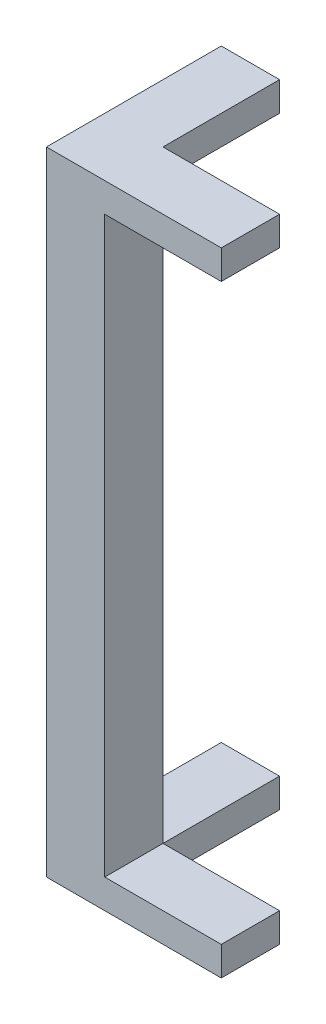
SolidWorks part; units mm, degrees
ref_plane "Front Plane" through (0, 0, 0) normal (0, 0, 1) x (1, 0, 0)
ref_plane "Top Plane" through (0, 0, 0) normal (0, 1, 0) x (1, 0, 0)
ref_plane "Right Plane" through (0, 0, 0) normal (1, 0, 0) x (0, 0, -1)
sketch "Sketch1" plane through (0, 0, 0) normal (0, 1, 0) x (1, 0, 0)
  line L1 (0, 0) -> (30, 0)
  line L2 (0, 0) -> (0, 10)
  line L3 (0, 10) -> (30, 10)
  line L4 (30, 0) -> (30, 10)
  line L5 (0, 0) -> (10, 0)
  line L6 (0, 0) -> (0, 30)
  line L7 (0, 30) -> (10, 30)
  line L8 (10, 0) -> (10, 30)
  dimension "D1" = 10
  dimension "D2" = 10
  dimension "D3" = 30
  dimension "D4" = 30
extrude "Boss-Extrude1" add sketch "Sketch1" along normal blind 10 contours L3 L8 L7 L6 | L1 L8 L3 L2 | L8 L1 L4 L3 region at (5, 0, -5) region at (20, 0, -5) region at (5, 0, -20)
sketch "Sketch2" plane through (0, 10, 0) normal (0, 1, 0) x (1, 0, 0)
  line L1 (0, 0) -> (10, 0)
  line L2 (0, 0) -> (0, 10)
  line L3 (0, 10) -> (10, 10)
  line L4 (10, 0) -> (10, 10)
extrude "Boss-Extrude2" add sketch "Sketch2" along normal blind 93.5
sketch "Sketch3" plane through (0, 103.5, 0) normal (0, 1, 0) x (1, 0, 0)
  line L1 (0, 0) -> (30, 0)
  line L2 (0, 0) -> (0, 10)
  line L3 (0, 10) -> (30, 10)
  line L4 (30, 0) -> (30, 10)
  line L5 (0, 0) -> (10, 0)
  line L6 (0, 0) -> (0, 30)
  line L7 (0, 30) -> (10, 30)
  line L8 (10, 0) -> (10, 30)
  line M9 (0, 10) -> (0, 0)
  line M10 (0, 0) -> (10, 0)
  line M11 (10, 0) -> (10, 10)
  line M12 (10, 10) -> (0, 10)
  dimension "D1" = 10
  dimension "D2" = 30
  dimension "D3" = 10
  dimension "D4" = 30
extrude "Boss-Extrude3" add sketch "Sketch3" along normal blind 5 contours L8 L7 L6 M12 | M12 M9 M10 M11 | L1 L4 L3 M11 region at (5, 103.5, -5) region at (20, 103.5, -5) region at (5, 103.5, -20)
sketch "Sketch4" plane through (0, 10, 0) normal (0, 1, 0) x (1, 0, 0)
  line L1 (30, 10) -> (10, 10)
  line L2 (30, 10) -> (30, 0)
  line L3 (30, 0) -> (10, 0)
  line L4 (10, 10) -> (10, 0)
  line L5 (10, 30) -> (0, 30)
  line L6 (10, 30) -> (10, 10)
  line L7 (10, 10) -> (0, 10)
  line L8 (0, 30) -> (0, 10)
  line M1 (10, 10) -> (10, 0)
  line M2 (10, 0) -> (30, 0)
  line M3 (30, 0) -> (30, 10)
  line M4 (30, 10) -> (10, 10)
extrude "Cut-Extrude1" cut sketch "Sketch4" against normal blind 5 contours L5 L8 L7 L6 | M4 M1 M2 M3 region at (20, 10, -5) region at (5, 10, -20)
